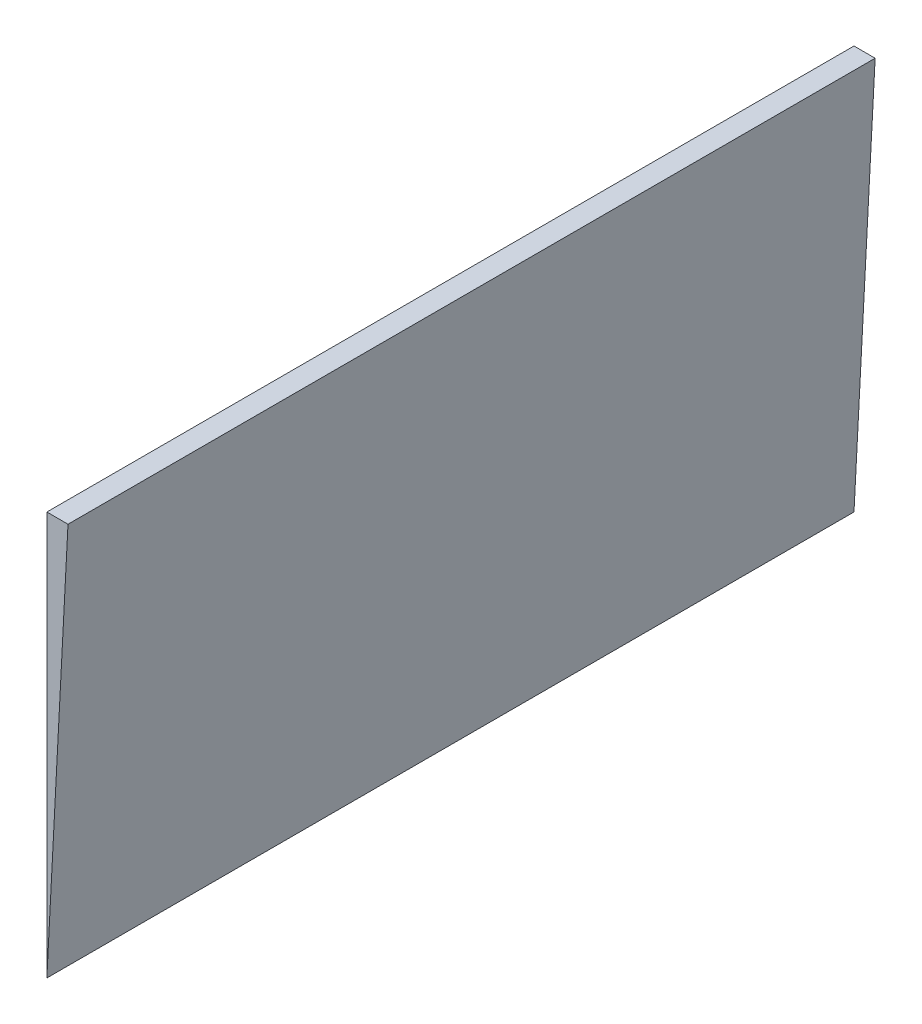
SolidWorks part; units mm, degrees
ref_plane "Front Plane" through (0, 0, 0) normal (0, 0, 1) x (1, 0, 0)
ref_plane "Top Plane" through (0, 0, 0) normal (0, 1, 0) x (1, 0, 0)
ref_plane "Right Plane" through (0, 0, 0) normal (1, 0, 0) x (0, 0, -1)
sketch "Sketch1" plane through (0, 0, 0) normal (0, 0, 1) x (1, 0, 0)
  line L0 (0, 25) -> (0, 0)
  line L1 (0, 0) -> (1.3102, 25)
  line L2 (1.3102, 25) -> (0, 25)
  point P2 (7.733, 19.0135)
  point P4 (0, 0)
  point P6 (0, 0)
  dimension "D1" = 3
  dimension "D2" = 25
extrude "Boss-Extrude1" add sketch "Sketch1" along normal blind 50
